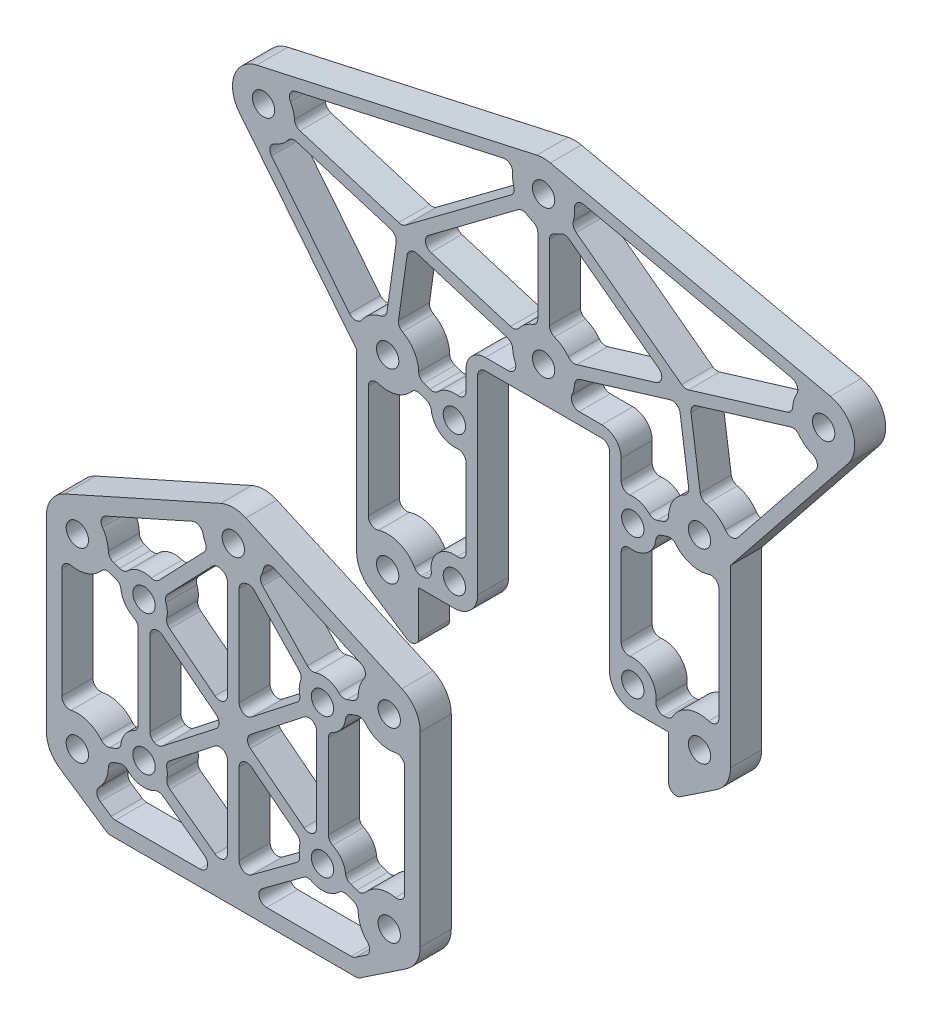
SolidWorks part; units mm, degrees
note: The reader was unsure of these and kept them because the rebuilt part matched: shared geometry of "Sketch1<3>", "Sketch4<3>".
material "6061-T6 (SS)"
ref_plane "Front Plane" through (0, 0, 0) normal (0, 0, 1) x (1, 0, 0)
ref_plane "Top Plane" through (0, 0, 0) normal (0, 1, 0) x (1, 0, 0)
ref_plane "Right Plane" through (0, 0, 0) normal (1, 0, 0) x (0, 0, -1)
sketch "Sketch1" plane through (0, 0, 0) normal (0, 0, 1) x (1, 0, 0)
  line L0 (-18.2562, -28.575) -> (18.2563, -28.575) construction
  line L1 (-23.0187, -9.525) -> (-23.0188, -19.05) construction
  line L3 (-25.5587, -19.05) -> (25.5587, -19.05)
  line L4 (-25.5587, -19.05) -> (-25.5588, -25.4)
  line L5 (-18.2562, -28.575) -> (18.2563, -28.575) construction
  line L6 (-23.0187, -9.525) -> (-23.0188, -19.05) construction
  line L8 (0, -28.575) -> (0, 0) construction
  line L9 (-158.75, -49.53) -> (-158.75, 49.53) construction
  line L10 (-23.0187, 0) -> (-23.0187, -9.525) construction
  line L11 (-25.5588, -25.4) -> (-31.9088, -25.4)
  line L12 (-23.0187, 0) -> (-23.0187, -9.525) construction
  line L13 (-38.2588, -19.05) -> (-38.2588, 19.05)
  line L14 (-165.1, 19.05) -> (-165.1, -19.05) construction
  line L15 (-31.9088, -19.05) -> (-31.9088, 19.05) construction
  line L16 (-31.9088, -19.05) -> (-165.1, -19.05) construction
  line L17 (-31.9088, 19.05) -> (-165.1, 19.05) construction
  line L18 (-13.4937, -12.3063) -> (-11.9062, -12.3063) construction
  line L19 (-11.9062, 12.3063) -> (-13.4937, 12.3063) construction
  line L20 (-13.4937, -12.3063) -> (-11.9062, -12.3063) construction
  line L21 (-11.9062, 12.3063) -> (-13.4937, 12.3063) construction
  line L22 (-13.4937, 12.3063) -> (-13.4937, -12.3063) construction
  line L23 (-13.4937, 0) -> (-31.9088, 0) construction
  line L24 (-31.9088, 0) -> (-165.1, 0) construction
  line L25 (-158.75, -49.53) -> (-158.75, 49.53) construction
  line L26 (-158.75, 0) -> (-165.1, 0) construction
  line L27 (-25.5587, -19.05) -> (-25.5587, -30.9562) construction
  line L28 (-36.8673, 15.0832) -> (-62.2673, 46.8332)
  line L29 (-57.3087, 57.15) -> (57.3087, 57.15)
  line L30 (36.8673, 15.0832) -> (62.2673, 46.8332)
  line L31 (38.2588, -19.05) -> (38.2588, 19.05)
  line L32 (25.5588, -25.4) -> (31.9088, -25.4)
  line L33 (25.5587, -19.05) -> (25.5588, -25.4)
  line L34 (-25.5587, -30.9562) -> (25.5588, -30.9562) construction
  line L35 (-25.5587, -30.9562) -> (25.5588, -30.9562)
  line L36 (-25.5587, -30.9562) -> (-35.4463, -24.3234)
  line L37 (25.5588, -30.9562) -> (35.4463, -24.3234)
  line L38 (-25.5588, -25.4) -> (-25.5587, -30.9562)
  line L39 (25.5588, -25.4) -> (25.5588, -30.9562)
  line L40 (-58.6826, 56.9996) -> (-1.3739, 69.6996)
  line L41 (58.6826, 56.9996) -> (1.3739, 69.6996)
  circle A0 centre (-31.9088, 19.05) radius 6.35 construction
  arc A1 (-57.3087, 57.15) -> (-62.2673, 46.8332) centre (-57.3087, 50.8) ccw
  circle A4 centre (-165.1, 19.05) radius 2.286
  circle A5 centre (-165.1, -19.05) radius 2.286
  circle A6 centre (-31.9088, -19.05) radius 2.286
  circle A7 centre (-31.9088, 19.05) radius 2.286
  arc A8 (-31.9088, -12.7) -> (-25.5587, -19.05) centre (-31.9088, -19.05) ccw
  circle A9 centre (-18.2563, -14.2875) radius 2.286 construction
  circle A10 centre (-18.2563, -14.2875) radius 2.286
  circle A11 centre (-57.3087, 50.8) radius 2.286
  arc A12 (57.3087, 57.15) -> (62.2673, 46.8332) centre (57.3087, 50.8) cw
  arc A13 (31.9088, -12.7) -> (25.5587, -19.05) centre (31.9088, -19.05) cw
  circle A14 centre (18.2563, -14.2875) radius 2.286
  circle A15 centre (31.9088, -19.05) radius 2.286
  circle A16 centre (31.9088, 19.05) radius 2.286
  circle A17 centre (57.3087, 50.8) radius 2.286
  circle A18 centre (0, 63.5) radius 6.35
  circle A19 centre (0, 63.5) radius 2.286
  point P3 (-31.9088, 0)
  point P48 (0, 57.15)
  point P58 (0, -19.05)
  dimension "D1" = 4.572
  dimension "D2" = 12.7
  dimension "D5" = 12.7
  dimension "D6" = 4.572
  dimension "D9" = 12.7
  dimension "D3" = 38.1
  dimension "D4" = 6.35
  dimension "D7" = 31.75
  dimension "D8" = 25.4
extrude "Boss-Extrude1" add sketch "Sketch1" along normal blind 6.35
extrude "Boss-Extrude2" add sketch "Sketch1<3>" against normal blind 6.35 from surface at -57.15 separate body
sketch "Sketch1<3>" plane through (0, 0, 0) normal (0, 0, 1) x (1, 0, 0) same geometry as "Sketch1"
fillet "Fillet1" radius 1.5875 2 edges at (25.5587, -30.9562, -60.325) (-25.5587, -30.9562, -60.325)
fillet "Fillet2" radius 1.5875 2 edges at (25.5588, -30.9562, 3.175) (-25.5587, -30.9562, 3.175)
sketch "Sketch3" plane through (0, 0, -63.5) normal (0, 0, -1) x (-1, 0, 0)
  line L0 (11.9062, 26.1938) -> (-11.9062, 26.1938)
  line L16 (-18.2563, -28.575) -> (18.2563, -28.575)
  line L17 (18.2563, -28.575) -> (18.2563, -19.05)
  line L18 (18.2563, -19.05) -> (23.0187, -19.05)
  line L19 (23.0187, -19.05) -> (23.0187, -9.525)
  line L20 (23.0187, -9.525) -> (18.2563, -9.525)
  line L21 (18.2563, -9.525) -> (18.2563, 0)
  line L22 (18.2563, 0) -> (13.4937, 0)
  line L23 (13.4937, 0) -> (13.4937, -24.6062)
  line L24 (11.9062, -26.1937) -> (-11.9062, -26.1937)
  line L25 (-13.4937, -24.6062) -> (-13.4937, 0)
  line L26 (-13.4937, 0) -> (-18.2563, 0)
  line L27 (-18.2563, 0) -> (-18.2563, -9.525)
  line L28 (-18.2563, -9.525) -> (-23.0188, -9.525)
  line L29 (-23.0188, -9.525) -> (-23.0188, -19.05)
  line L30 (-23.0188, -19.05) -> (-18.2563, -19.05)
  line L31 (-18.2563, -19.05) -> (-18.2563, -28.575)
  line L39 (13.4937, 24.6063) -> (13.4937, -24.6062)
  line L40 (11.9062, -26.1937) -> (-11.9062, -26.1937)
  line L41 (-13.4937, -24.6062) -> (-13.4937, 24.6063)
  line L42 (-13.4937, 0) -> (-18.2563, 0) construction
  arc A0 (11.9062, 26.1938) -> (13.4937, 24.6063) centre (11.9062, 24.6063) cw
  arc A1 (-13.4937, 24.6063) -> (-11.9062, 26.1938) centre (-11.9062, 24.6063) cw
  arc A2 (11.9062, -26.1937) -> (13.4937, -24.6062) centre (11.9062, -24.6062) ccw
  arc A3 (-13.4937, -24.6062) -> (-11.9062, -26.1937) centre (-11.9062, -24.6062) ccw
  arc A4 (11.9062, -26.1937) -> (13.4937, -24.6062) centre (11.9062, -24.6062) ccw
  arc A5 (-13.4937, -24.6062) -> (-11.9062, -26.1937) centre (-11.9062, -24.6062) ccw
  dimension "D1" = 0
extrude "Cut-Extrude1" cut sketch "Sketch3" against normal blind 7.62
fillet "Fillet3" radius 4.7625 2 edges at (13.4937, -19.05, -60.325) (-13.4937, -19.05, -60.325)
sketch "Sketch4" plane through (0, 0, 6.35) normal (0, 0, 1) x (1, 0, 0)
  line L0 (-34.5038, 24.8455) -> (-2.595, 39.133)
  line L1 (34.5038, 24.8455) -> (2.595, 39.133)
  line L2 (-38.2588, 16.8225) -> (-38.2587, 19.05)
  line L3 (38.2588, 16.8225) -> (38.2588, 19.05)
  line L4 (38.2588, 16.8225) -> (125.4224, 90.4023)
  line L5 (125.4224, 90.4023) -> (-79.2317, 82.9092)
  line L6 (-79.2317, 82.9092) -> (-98.2459, 9.0775)
  line L7 (-98.2459, 9.0775) -> (-38.2588, 16.8225)
  circle A0 centre (-31.9088, 19.05) radius 6.35
  circle A1 centre (31.9088, 19.05) radius 6.35
  circle A2 centre (0, 33.3375) radius 6.35
  circle A3 centre (0, 33.3375) radius 2.286
  circle A4 centre (-18.2563, -14.2875) radius 2.286 construction
  circle A5 centre (-18.2563, 14.2875) radius 2.286
  circle A6 centre (18.2563, 14.2875) radius 2.286
  point P29 (18.2563, -14.2875)
  point P30 (-18.2563, -14.2875)
  dimension "D1" = 12.7
  dimension "D2" = 4.572
  dimension "D3" = 47.625
  dimension "D4" = 28.575
extrude "Cut-Extrude2" cut sketch "Sketch4" against normal blind 9.525
extrude "Cut-Extrude3" cut sketch "Sketch4<3>" against normal through all both and the other way through all contours A3 | A5 | A6
sketch "Sketch4<3>" plane through (0, 0, 6.35) normal (0, 0, 1) x (1, 0, 0) same geometry as "Sketch4"
sketch "Sketch5" plane through (0, 0, 6.35) normal (0, 0, 1) x (1, 0, 0)
  line L0 (-1.2975, 36.2353) -> (-33.2063, 21.9478)
  line L1 (-35.0837, 19.05) -> (-35.0837, -19.05)
  line L2 (-33.6775, -21.6867) -> (-24.5924, -27.7812)
  line L3 (-24.5924, -27.7812) -> (24.5924, -27.7812)
  line L4 (24.5924, -27.7812) -> (33.6775, -21.6867)
  line L5 (35.0838, -19.05) -> (35.0838, 19.05)
  line L6 (33.2063, 21.9478) -> (1.2975, 36.2353)
  line L7 (38.2588, -19.05) -> (38.2588, 19.05)
  line L8 (34.5038, 24.8455) -> (2.595, 39.133)
  line L9 (-2.595, 39.133) -> (-34.5038, 24.8455)
  line L10 (-38.2587, 19.05) -> (-38.2588, -19.05)
  line L11 (-35.4463, -24.3234) -> (-25.96, -30.6871)
  line L12 (-25.0756, -30.9562) -> (25.0756, -30.9562)
  line L13 (25.96, -30.6871) -> (35.4463, -24.3234)
  line L14 (38.2588, -19.05) -> (38.2588, 19.05)
  line L15 (34.5038, 24.8455) -> (2.595, 39.133)
  line L16 (-2.595, 39.133) -> (-34.5038, 24.8455)
  line L17 (-38.2587, 19.05) -> (-38.2588, -19.05)
  line L18 (-35.4463, -24.3234) -> (-25.96, -30.6871)
  line L19 (-25.0756, -30.9562) -> (25.0756, -30.9562)
  line L20 (25.96, -30.6871) -> (35.4463, -24.3234)
  line L21 (-31.9088, 19.05) -> (-18.2563, 14.2875)
  line L22 (18.2563, 14.2875) -> (31.9088, 19.05)
  line L23 (18.2563, -14.2875) -> (31.9088, -19.05)
  line L24 (-18.2563, -14.2875) -> (-31.9088, -19.05)
  line L25 (0, 33.3375) -> (0, -27.7812)
  line L26 (-18.2563, 14.2875) -> (18.2563, -14.2875)
  line L27 (18.2563, 14.2875) -> (-18.2563, -14.2875)
  line L28 (-18.2563, -14.2875) -> (0, -27.7812)
  line L29 (0, -27.7812) -> (18.2563, -14.2875)
  line L30 (0, 33.3375) -> (-18.2563, 14.2875)
  line L31 (0, 33.3375) -> (18.2563, 14.2875)
  line L32 (-18.2563, 14.2875) -> (-18.2563, -14.2875)
  line L33 (18.2563, 14.2875) -> (18.2563, -14.2875)
  line L34 (-19.4469, 14.2875) -> (-19.4469, -14.2875)
  line L35 (-18.99, 13.3499) -> (17.5225, -15.2251)
  line L36 (-32.3009, 17.9258) -> (-18.6484, 13.1633)
  line L37 (-0.8596, 34.1613) -> (-19.1159, 15.1113)
  line L38 (-0.8596, 32.5137) -> (17.3966, 13.4637)
  line L39 (-1.1906, 33.3375) -> (-1.1906, -27.7812)
  line L40 (17.5225, 15.2251) -> (-18.99, -13.3499)
  line L41 (18.6484, 13.1633) -> (32.3009, 17.9258)
  line L42 (17.8641, -15.4117) -> (31.5166, -20.1742)
  line L43 (0.7077, -28.7387) -> (18.9639, -15.245)
  line L44 (-18.9639, -15.245) -> (-0.7077, -28.7387)
  line L45 (-18.6484, -13.1633) -> (-32.3009, -17.9258)
  line L46 (17.0656, 14.2875) -> (17.0656, -14.2875)
  line L47 (-17.0656, 14.2875) -> (-17.0656, -14.2875)
  line L48 (-17.5225, 15.2251) -> (18.99, -13.3499)
  line L49 (-31.5166, 20.1742) -> (-17.8641, 15.4117)
  line L50 (0.8596, 32.5137) -> (-17.3966, 13.4637)
  line L51 (0.8596, 34.1613) -> (19.1159, 15.1113)
  line L52 (1.1906, 33.3375) -> (1.1906, -27.7812)
  line L53 (18.99, 13.3499) -> (-17.5225, -15.2251)
  line L54 (17.8641, 15.4117) -> (31.5166, 20.1742)
  line L55 (18.6484, -13.1633) -> (32.3009, -17.9258)
  line L56 (-0.7077, -26.8238) -> (17.5486, -13.33)
  line L57 (-17.5486, -13.33) -> (0.7077, -26.8238)
  line L58 (-17.8641, -15.4117) -> (-31.5166, -20.1742)
  line L59 (19.4469, 14.2875) -> (19.4469, -14.2875)
  circle A0 centre (-31.9088, 19.05) radius 6.35
  circle A1 centre (-18.2563, 14.2875) radius 2.286
  circle A2 centre (-18.2563, 14.2875) radius 2.286
  circle A3 centre (0, 33.3375) radius 2.286
  circle A4 centre (0, 33.3375) radius 2.286
  circle A5 centre (31.9088, 19.05) radius 2.286
  circle A6 centre (31.9088, 19.05) radius 2.286
  circle A7 centre (18.2563, -14.2875) radius 2.286
  circle A8 centre (18.2563, -14.2875) radius 2.286
  circle A9 centre (-18.2563, -14.2875) radius 2.286
  circle A10 centre (-18.2563, -14.2875) radius 2.286
  circle A11 centre (-31.9088, 19.05) radius 2.286
  circle A12 centre (-31.9088, 19.05) radius 2.286
  circle A13 centre (-31.9088, -19.05) radius 2.286
  circle A14 centre (-31.9088, -19.05) radius 2.286
  circle A15 centre (31.9088, -19.05) radius 2.286
  circle A16 centre (31.9088, -19.05) radius 2.286
  circle A17 centre (18.2563, 14.2875) radius 2.286
  circle A18 centre (18.2563, 14.2875) radius 2.286
  circle A19 centre (-31.9088, -19.05) radius 6.35
  circle A20 centre (31.9088, -19.05) radius 6.35
  circle A21 centre (31.9088, 19.05) radius 6.35
  circle A22 centre (0, 33.3375) radius 6.35
  circle A23 centre (-18.2563, 14.2875) radius 4.7625
  circle A24 centre (-18.2563, -14.2875) radius 4.7625
  arc A25 (38.2588, 19.05) -> (34.5038, 24.8455) centre (31.9088, 19.05) ccw
  arc A26 (2.595, 39.133) -> (-2.595, 39.133) centre (0, 33.3375) ccw
  arc A27 (-34.5038, 24.8455) -> (-38.2587, 19.05) centre (-31.9088, 19.05) ccw
  arc A28 (-38.2588, -19.05) -> (-35.4463, -24.3234) centre (-31.9088, -19.05) ccw
  arc A29 (-25.96, -30.6871) -> (-25.0756, -30.9562) centre (-25.0756, -29.3687) ccw
  arc A30 (25.0756, -30.9562) -> (25.96, -30.6871) centre (25.0756, -29.3687) ccw
  arc A31 (35.4463, -24.3234) -> (38.2588, -19.05) centre (31.9088, -19.05) ccw
  arc A32 (38.2588, 19.05) -> (34.5038, 24.8455) centre (31.9088, 19.05) ccw
  arc A33 (2.595, 39.133) -> (-2.595, 39.133) centre (0, 33.3375) ccw
  arc A34 (-34.5038, 24.8455) -> (-38.2587, 19.05) centre (-31.9088, 19.05) ccw
  arc A35 (-38.2588, -19.05) -> (-35.4463, -24.3234) centre (-31.9088, -19.05) ccw
  arc A36 (-25.96, -30.6871) -> (-25.0756, -30.9562) centre (-25.0756, -29.3687) ccw
  arc A37 (25.0756, -30.9562) -> (25.96, -30.6871) centre (25.0756, -29.3687) ccw
  arc A38 (35.4463, -24.3234) -> (38.2588, -19.05) centre (31.9088, -19.05) ccw
  circle A39 centre (18.2563, -14.2875) radius 4.7625
  circle A40 centre (18.2563, 14.2875) radius 4.7625
  arc A41 (-33.2063, 21.9478) -> (-35.0837, 19.05) centre (-31.9088, 19.05) ccw
  arc A42 (-35.0837, -19.05) -> (-33.6775, -21.6867) centre (-31.9088, -19.05) ccw
  arc A43 (-24.5924, -27.7812) -> (-24.5924, -27.7812) centre (-24.5924, -27.7812) ccw
  arc A44 (24.5924, -27.7812) -> (24.5924, -27.7812) centre (24.5924, -27.7812) ccw
  arc A45 (33.6775, -21.6867) -> (35.0838, -19.05) centre (31.9088, -19.05) ccw
  arc A46 (35.0838, 19.05) -> (33.2063, 21.9478) centre (31.9088, 19.05) ccw
  arc A47 (1.2975, 36.2353) -> (-1.2975, 36.2353) centre (0, 33.3375) ccw
  dimension "D1" = 0
  dimension "D2" = 0
  dimension "D3" = 0
  dimension "D4" = 0
  dimension "D5" = 0
  dimension "D6" = 0
  dimension "D7" = 0
  dimension "D8" = 0
  dimension "D9" = 0
  dimension "D10" = 0
  dimension "D11" = 2.4765
  dimension "D12" = 3.175
  dimension "D13" = 1.1906
  dimension "D14" = 1.1906
extrude "Cut-Extrude4" cut sketch "Sketch5" against normal blind 7.62 contours A23 L37 A22 L0 A0 L49 | A24 L34 A23 L36 A0 L1 A19 L45 | A24 L40 L35 A23 L47 | A24 L58 A19 L2 L3 L44 | A24 L57 L39 L53 | A39 L35 L52 L56 | A39 L43 L3 L4 A20 L42 | A40 L59 A39 L55 A20 L5 A21 L41 | A40 L53 L48 A39 L46 | A40 L38 A22 L52 L40 | A23 L48 L39 A22 L50 | A40 L54 A21 L6 A22 L51
fillet "Fillet4" radius 1.5875 68 edges at (-15.2557, -17.9859, 3.175) (-2.0031, -27.7812, 3.175) (-24.5924, -27.7812, 3.175) (-29.1107, -24.7503, 3.175) (-25.6273, -18.1198, 3.175) (-22.2181, -16.9305, 3.175) (-17.0656, -9.6762, 3.175) (-17.0656, 9.6762, 3.175) (-15.3586, 10.5079, 3.175) (-1.9319, 0, 3.175) (-15.3586, -10.5079, 3.175) (17.0656, 9.6762, 3.175) (17.0656, -9.6762, 3.175) (15.3586, -10.5079, 3.175) (1.9319, 0, 3.175) (15.3586, 10.5079, 3.175) (13.8403, -16.0709, 3.175) (1.1906, -25.4207, 3.175) (1.1906, -2.4437, 3.175) (13.8911, -12.3832, 3.175) (15.9253, 18.4406, 3.175) (5.1753, 29.658, 3.175) (6.3166, 33.9879, 3.175) (28.1872, 24.1951, 3.175) (25.6273, 18.1198, 3.175) (22.2181, 16.9305, 3.175) (13.8911, 12.3832, 3.175) (1.1906, 2.4437, 3.175) (1.1906, 27.1001, 3.175) (3.4561, 28.0104, 3.175) (14.2061, 16.793, 3.175) (-22.2181, 16.9305, 3.175) (-25.6273, 18.1198, 3.175) (-28.1872, 24.1951, 3.175) (-6.3166, 33.9879, 3.175) (-5.1753, 29.658, 3.175) (-15.9253, 18.4406, 3.175) (-14.2061, 16.793, 3.175) (-3.4561, 28.0104, 3.175) (-1.1906, 27.1001, 3.175) (-1.1906, 2.4437, 3.175) (-13.8911, 12.3832, 3.175) (22.2181, -16.9305, 3.175) (25.6273, -18.1198, 3.175) (29.1107, -24.7503, 3.175) (24.5924, -27.7812, 3.175) (2.0031, -27.7812, 3.175) (15.2557, -17.9859, 3.175) (23.0024, 14.6821, 3.175) (26.4116, 15.8714, 3.175) (35.0838, 13.5507, 3.175) (35.0838, -13.5507, 3.175) (26.4116, -15.8714, 3.175) (23.0024, -14.6821, 3.175) (19.4469, -9.6762, 3.175) (19.4469, 9.6762, 3.175) (-23.0024, -14.6821, 3.175) (-26.4116, -15.8714, 3.175) (-35.0837, -13.5507, 3.175) (-26.4116, 15.8714, 3.175) (-23.0024, 14.6821, 3.175) (-19.4469, 9.6762, 3.175) (-19.4469, -9.6762, 3.175) (-13.8911, -12.3832, 3.175) (-1.1906, -2.4437, 3.175) (-1.1906, -25.4207, 3.175) (-13.8403, -16.0709, 3.175) (-35.0837, 13.5507, 3.175)
sketch "Sketch6" plane through (0, 0, -63.5) normal (0, 0, -1) x (-1, 0, 0)
  line L0 (-60.4078, 48.3207) -> (-35.8775, 17.6578)
  line L1 (-35.8775, 17.6578) -> (-35.8775, -19.05)
  line L2 (-34.1197, -22.3458) -> (-27.94, -26.4914)
  line L3 (-27.94, -26.4914) -> (-27.94, -16.6687)
  line L4 (-27.94, -16.6687) -> (-18.2563, -16.6687)
  line L5 (-15.875, -14.2875) -> (-15.875, 24.6063)
  line L6 (-11.9063, 28.575) -> (11.9062, 28.575)
  line L7 (15.875, 24.6063) -> (15.875, -14.2875)
  line L8 (18.2562, -16.6687) -> (27.94, -16.6687)
  line L9 (27.94, -16.6687) -> (27.94, -26.4914)
  line L10 (27.94, -26.4914) -> (34.1197, -22.3458)
  line L11 (35.8775, -19.05) -> (35.8775, 17.6578)
  line L12 (35.8775, 17.6578) -> (60.4078, 48.3207)
  line L13 (58.1674, 54.6747) -> (0.8587, 67.3747)
  line L14 (-0.8587, 67.3747) -> (-58.1674, 54.6747)
  line L15 (-25.5587, -19.05) -> (-18.2563, -19.05)
  line L16 (-13.4937, -14.2875) -> (-13.4937, 24.6063)
  line L17 (-11.9062, 26.1938) -> (11.9062, 26.1938)
  line L18 (13.4937, 24.6063) -> (13.4937, -14.2875)
  line L19 (18.2562, -19.05) -> (25.5588, -19.05)
  line L20 (25.5588, -19.05) -> (25.5588, -27.9797)
  line L21 (28.0306, -29.298) -> (35.4463, -24.3234)
  line L22 (38.2588, -19.05) -> (38.2588, 16.8225)
  line L23 (38.2588, 16.8225) -> (62.2673, 46.8332)
  line L24 (58.6826, 56.9996) -> (1.3739, 69.6996)
  line L25 (-1.3739, 69.6996) -> (-58.6826, 56.9996)
  line L26 (-62.2673, 46.8332) -> (-38.2588, 16.8225)
  line L27 (-38.2588, 16.8225) -> (-38.2588, -19.05)
  line L28 (-35.4463, -24.3234) -> (-28.0306, -29.298)
  line L29 (-25.5588, -27.9797) -> (-25.5587, -19.05)
  line L30 (-25.5587, -19.05) -> (-18.2563, -19.05)
  line L31 (-13.4937, -14.2875) -> (-13.4937, 24.6063)
  line L32 (-11.9062, 26.1938) -> (11.9062, 26.1938)
  line L33 (13.4937, 24.6063) -> (13.4937, -14.2875)
  line L34 (18.2562, -19.05) -> (25.5588, -19.05)
  line L35 (25.5588, -19.05) -> (25.5588, -27.9797)
  line L36 (28.0306, -29.298) -> (35.4463, -24.3234)
  line L37 (38.2588, -19.05) -> (38.2588, 16.8225)
  line L38 (38.2588, 16.8225) -> (62.2673, 46.8332)
  line L39 (58.6826, 56.9996) -> (1.3739, 69.6996)
  line L40 (-1.3739, 69.6996) -> (-58.6826, 56.9996)
  line L41 (-62.2673, 46.8332) -> (-38.2588, 16.8225)
  line L42 (-38.2588, 16.8225) -> (-38.2588, -19.05)
  line L43 (-35.4463, -24.3234) -> (-28.0306, -29.298)
  line L44 (-25.5588, -27.9797) -> (-25.5587, -19.05)
  line L45 (-18.2563, 14.2875) -> (-31.9088, 19.05)
  line L46 (18.2563, 14.2875) -> (31.9088, 19.05)
  line L47 (0, 63.5) -> (0, 33.3375)
  line L48 (0, 33.3375) -> (57.3087, 50.8)
  line L49 (31.9088, 19.05) -> (28.6544, 42.0688)
  line L50 (28.6544, 42.0688) -> (0, 63.5)
  line L51 (0, 33.3375) -> (-57.3087, 50.8)
  line L52 (-31.9088, 19.05) -> (-28.6544, 42.0688)
  line L53 (-28.6544, 42.0688) -> (0, 63.5)
  line L54 (0.347, 32.1986) -> (57.6558, 49.6611)
  line L55 (18.6484, 13.1633) -> (33.2246, 18.248)
  line L56 (33.2246, 18.248) -> (29.764, 42.7257)
  line L57 (29.764, 42.7257) -> (0.7131, 64.4534)
  line L58 (-1.1906, 63.5) -> (-1.1906, 33.3375)
  line L59 (-17.8641, 15.4117) -> (-30.5929, 19.852)
  line L60 (-30.5929, 19.852) -> (-27.5448, 41.4118)
  line L61 (-27.5448, 41.4118) -> (0.7131, 62.5466)
  line L62 (0.347, 34.4764) -> (-56.9617, 51.9389)
  line L63 (-0.347, 34.4764) -> (56.9617, 51.9389)
  line L64 (17.8641, 15.4117) -> (30.5929, 19.852)
  line L65 (30.5929, 19.852) -> (27.5448, 41.4118)
  line L66 (27.5448, 41.4118) -> (-0.7131, 62.5466)
  line L67 (1.1906, 63.5) -> (1.1906, 33.3375)
  line L68 (-18.6484, 13.1633) -> (-33.2246, 18.248)
  line L69 (-33.2246, 18.248) -> (-29.764, 42.7257)
  line L70 (-29.764, 42.7257) -> (-0.7131, 64.4534)
  line L71 (-0.347, 32.1986) -> (-57.6558, 49.6611)
  circle A0 centre (-57.3087, 50.8) radius 6.35
  circle A1 centre (31.9088, -19.05) radius 2.286
  circle A2 centre (31.9088, -19.05) radius 2.286
  circle A3 centre (-31.9088, -19.05) radius 2.286
  circle A4 centre (-31.9088, -19.05) radius 2.286
  circle A5 centre (-57.3087, 50.8) radius 2.286
  circle A6 centre (-57.3087, 50.8) radius 2.286
  circle A7 centre (0, 33.3375) radius 2.286
  circle A8 centre (0, 33.3375) radius 2.286
  circle A9 centre (-18.2563, 14.2875) radius 2.286
  circle A10 centre (-18.2563, 14.2875) radius 2.286
  circle A11 centre (0, 63.5) radius 2.286
  circle A12 centre (0, 63.5) radius 2.286
  circle A13 centre (-31.9088, 19.05) radius 2.286
  circle A14 centre (-31.9088, 19.05) radius 2.286
  circle A15 centre (-18.2563, -14.2875) radius 2.286
  circle A16 centre (-18.2563, -14.2875) radius 2.286
  circle A17 centre (57.3087, 50.8) radius 2.286
  circle A18 centre (57.3087, 50.8) radius 2.286
  circle A19 centre (18.2563, -14.2875) radius 2.286
  circle A20 centre (18.2563, -14.2875) radius 2.286
  circle A21 centre (31.9088, 19.05) radius 2.286
  circle A22 centre (31.9088, 19.05) radius 2.286
  circle A23 centre (18.2563, 14.2875) radius 2.286
  circle A24 centre (18.2563, 14.2875) radius 2.286
  circle A25 centre (0, 63.5) radius 6.35
  circle A26 centre (57.3087, 50.8) radius 6.35
  circle A27 centre (31.9088, 19.05) radius 6.35
  circle A28 centre (31.9088, -19.05) radius 6.35
  circle A29 centre (-31.9088, -19.05) radius 6.35
  circle A30 centre (-18.2562, -14.2875) radius 4.7625
  circle A31 centre (18.2562, -14.2875) radius 4.7625
  circle A32 centre (18.2563, 14.2875) radius 4.7625
  circle A33 centre (-18.2563, 14.2875) radius 4.7625
  circle A34 centre (-31.9088, 19.05) radius 6.35
  arc A35 (-18.2563, -19.05) -> (-13.4937, -14.2875) centre (-18.2562, -14.2875) ccw
  arc A36 (-11.9062, 26.1938) -> (-13.4937, 24.6063) centre (-11.9062, 24.6063) ccw
  arc A37 (13.4937, 24.6063) -> (11.9062, 26.1938) centre (11.9062, 24.6063) ccw
  arc A38 (13.4937, -14.2875) -> (18.2562, -19.05) centre (18.2562, -14.2875) ccw
  arc A39 (25.5588, -27.9797) -> (28.0306, -29.298) centre (27.1463, -27.9797) ccw
  arc A40 (35.4463, -24.3234) -> (38.2588, -19.05) centre (31.9088, -19.05) ccw
  arc A41 (62.2673, 46.8332) -> (58.6826, 56.9996) centre (57.3087, 50.8) ccw
  arc A42 (1.3739, 69.6996) -> (-1.3739, 69.6996) centre (0, 63.5) ccw
  arc A43 (-58.6826, 56.9996) -> (-62.2673, 46.8332) centre (-57.3087, 50.8) ccw
  arc A44 (-38.2588, -19.05) -> (-35.4463, -24.3234) centre (-31.9088, -19.05) ccw
  arc A45 (-28.0306, -29.298) -> (-25.5588, -27.9797) centre (-27.1463, -27.9797) ccw
  arc A46 (-18.2563, -19.05) -> (-13.4937, -14.2875) centre (-18.2562, -14.2875) ccw
  arc A47 (-11.9062, 26.1938) -> (-13.4937, 24.6063) centre (-11.9062, 24.6063) ccw
  arc A48 (13.4937, 24.6063) -> (11.9062, 26.1938) centre (11.9062, 24.6063) ccw
  arc A49 (13.4937, -14.2875) -> (18.2562, -19.05) centre (18.2562, -14.2875) ccw
  arc A50 (25.5588, -27.9797) -> (28.0306, -29.298) centre (27.1463, -27.9797) ccw
  arc A51 (35.4463, -24.3234) -> (38.2588, -19.05) centre (31.9088, -19.05) ccw
  arc A52 (62.2673, 46.8332) -> (58.6826, 56.9996) centre (57.3087, 50.8) ccw
  arc A53 (1.3739, 69.6996) -> (-1.3739, 69.6996) centre (0, 63.5) ccw
  arc A54 (-58.6826, 56.9996) -> (-62.2673, 46.8332) centre (-57.3087, 50.8) ccw
  arc A55 (-38.2588, -19.05) -> (-35.4463, -24.3234) centre (-31.9088, -19.05) ccw
  arc A56 (-28.0306, -29.298) -> (-25.5588, -27.9797) centre (-27.1463, -27.9797) ccw
  circle A57 centre (0, 33.3375) radius 6.35
  arc A58 (-35.8775, -19.05) -> (-34.1197, -22.3458) centre (-31.9088, -19.05) ccw
  arc A59 (-27.94, -26.4914) -> (-27.94, -26.4914) centre (-27.94, -26.4914) ccw
  arc A60 (-18.2563, -16.6687) -> (-15.875, -14.2875) centre (-18.2562, -14.2875) ccw
  arc A61 (-11.9063, 28.575) -> (-15.875, 24.6063) centre (-11.9062, 24.6063) ccw
  arc A62 (15.875, 24.6063) -> (11.9062, 28.575) centre (11.9062, 24.6063) ccw
  arc A63 (15.875, -14.2875) -> (18.2562, -16.6687) centre (18.2562, -14.2875) ccw
  arc A64 (27.94, -26.4914) -> (27.94, -26.4914) centre (27.94, -26.4914) ccw
  arc A65 (34.1197, -22.3458) -> (35.8775, -19.05) centre (31.9088, -19.05) ccw
  arc A66 (60.4078, 48.3207) -> (58.1674, 54.6747) centre (57.3087, 50.8) ccw
  arc A67 (0.8587, 67.3747) -> (-0.8587, 67.3747) centre (0, 63.5) ccw
  arc A68 (-58.1674, 54.6747) -> (-60.4078, 48.3207) centre (-57.3087, 50.8) ccw
  dimension "D1" = 0
  dimension "D2" = 0
  dimension "D3" = 0
  dimension "D4" = 0
  dimension "D5" = 0
  dimension "D6" = 0
  dimension "D7" = 0
  dimension "D8" = 0
  dimension "D9" = 0
  dimension "D10" = 0
  dimension "D11" = 0
  dimension "D12" = 0
  dimension "D13" = 0
  dimension "D14" = 2.3813
  dimension "D15" = 1.1906
  dimension "D16" = 1.1906
extrude "Cut-Extrude5" cut sketch "Sketch6" against normal blind 7.62 contours A34 L1 A29 L4 A30 L5 A33 L68 | A61 L6 A57 L71 L60 A34 L59 A33 L5 | A34 L69 L71 A0 L0 | A25 L14 A0 L62 L70 | A57 L58 A25 L61 L62 | A57 L63 L66 A25 L67 | A26 L13 A25 L57 L63 | A62 L7 A32 L64 A27 L65 L54 A57 L6 | A27 L12 A26 L54 L56 | A32 L7 A31 L8 A28 L11 A27 L55 | L41 L42 A55 L43 A56 L44 L30 A46 L31 A47 L32 A48 L33 A49 L34 L35 A50 L36 A51 L37 L38 A52 L39 A53 L40 A54
fillet "Fillet5" radius 1.5875 60 edges at (-26.4116, 15.8714, -60.325) (-35.8775, 14.093, -60.325) (-35.8775, -14.093, -60.325) (-26.0221, -16.6688, -60.325) (-22.3807, -16.6688, -60.325) (-15.875, -10.1631, -60.325) (-15.875, 10.1631, -60.325) (-15.875, 18.4119, -60.325) (-23.0024, 14.6821, -60.325) (-28.8844, 43.3835, -60.325) (-5.708, 60.7177, -60.325) (-5.6982, 66.3023, -60.325) (-53.3279, 55.7472, -60.325) (-50.9952, 50.1209, -60.325) (-1.1906, 57.2626, -60.325) (-4.2818, 58.8108, -60.325) (-26.0595, 42.5227, -60.325) (-5.6195, 36.2945, -60.325) (-1.1906, 39.5749, -60.325) (-4.2001, 28.575, -60.325) (4.2001, 28.575, -60.325) (-6.3136, 34.0166, -60.325) (-27.6703, 40.5242, -60.325) (-29.8567, 25.0593, -60.325) (-25.6273, 18.1198, -60.325) (-22.2181, 16.9305, -60.325) (-29.9759, 41.2268, -60.325) (-51.6893, 47.843, -60.325) (-57.3112, 44.45, -60.325) (-38.1044, 20.4415, -60.325) (-32.2145, 25.3926, -60.325) (15.875, 18.4119, -60.325) (15.875, 10.1631, -60.325) (22.2181, 16.9305, -60.325) (25.6273, 18.1198, -60.325) (29.8567, 25.0593, -60.325) (27.6703, 40.5242, -60.325) (6.3136, 34.0166, -60.325) (57.3112, 44.45, -60.325) (51.6893, 47.843, -60.325) (29.9759, 41.2268, -60.325) (32.2145, 25.3926, -60.325) (38.1044, 20.4415, -60.325) (26.0595, 42.5227, -60.325) (4.2818, 58.8108, -60.325) (1.1906, 57.2626, -60.325) (1.1906, 39.5749, -60.325) (5.6195, 36.2945, -60.325) (28.8844, 43.3835, -60.325) (50.9952, 50.1209, -60.325) (53.3279, 55.7472, -60.325) (5.6982, 66.3023, -60.325) (5.708, 60.7177, -60.325) (23.0024, 14.6821, -60.325) (15.875, -10.1631, -60.325) (22.3807, -16.6688, -60.325) (35.8775, -14.093, -60.325) (35.8775, 14.093, -60.325) (26.4116, 15.8714, -60.325) (26.0221, -16.6688, -60.325)
